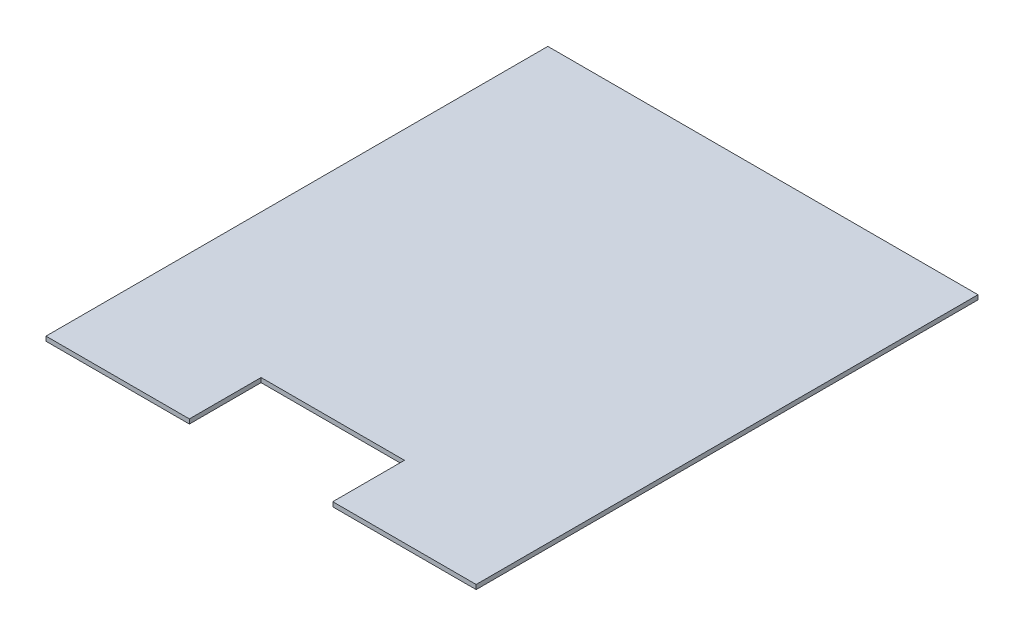
SolidWorks part; units mm, degrees
ref_plane "Front Plane" through (0, 0, 0) normal (0, 0, 1) x (1, 0, 0)
ref_plane "Top Plane" through (0, 0, 0) normal (0, 1, 0) x (1, 0, 0)
ref_plane "Right Plane" through (0, 0, 0) normal (1, 0, 0) x (0, 0, -1)
sketch "Sketch1" plane through (0, 0, 0) normal (0, 1, 0) x (1, 0, 0)
  line L1 (-152.4, -177.8) -> (152.4, -177.8)
  line L2 (-152.4, -177.8) -> (-152.4, 177.8)
  line L3 (-152.4, 177.8) -> (152.4, 177.8)
  line L4 (152.4, -177.8) -> (152.4, 177.8)
  line L5 (-152.4, -177.8) -> (152.4, 177.8) construction
  line L6 (-152.4, 177.8) -> (152.4, -177.8) construction
  point P0 (0, 0)
  dimension "D1" = 355.6
  dimension "D2" = 304.8
extrude "Boss-Extrude1" add sketch "Sketch1" along normal blind 3.175
sketch "Sketch2" plane through (0, 3.175, 0) normal (0, 1, 0) x (1, 0, 0)
  line L0 (-152.4, -177.8) -> (152.4, -177.8) construction
  line L1 (-50.8, -127) -> (50.8, -127)
  line L2 (-50.8, -127) -> (-50.8, -177.8)
  line L3 (-50.8, -177.8) -> (50.8, -177.8)
  line L4 (50.8, -127) -> (50.8, -177.8)
  line L5 (-50.8, -127) -> (50.8, -177.8) construction
  line L6 (-50.8, -177.8) -> (50.8, -127) construction
  point P0 (0, -152.4)
  dimension "D1" = 50.8
  dimension "D2" = 101.6
extrude "Cut-Extrude1" cut sketch "Sketch2" against normal blind 3.175
